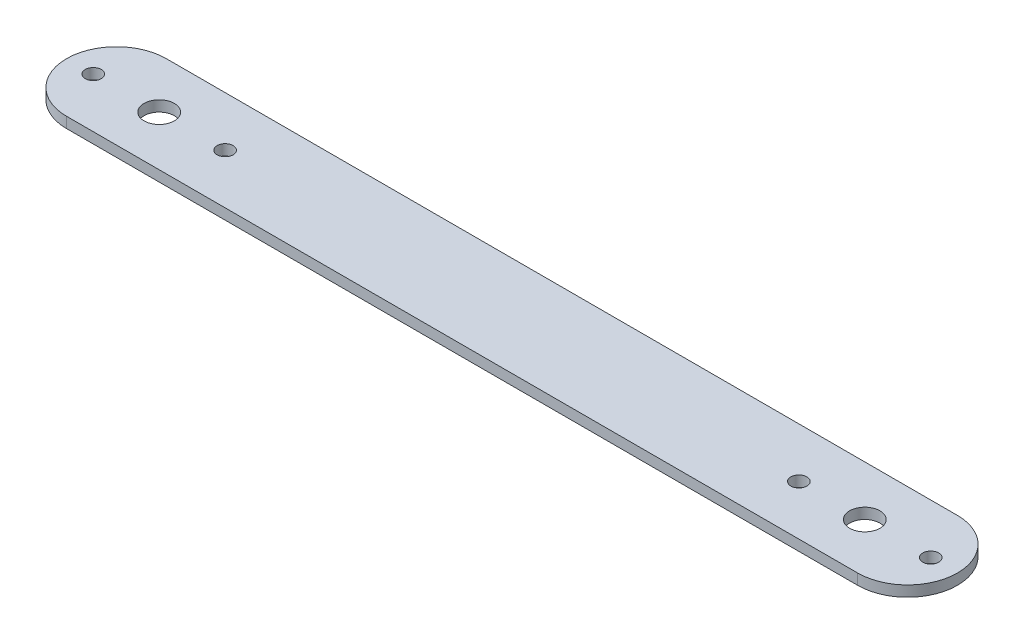
SolidWorks part; units mm, degrees
ref_plane "前视" through (0, 0, 0) normal (0, 0, 1) x (1, 0, 0)
ref_plane "上视" through (0, 0, 0) normal (0, 1, 0) x (1, 0, 0)
ref_plane "右视" through (0, 0, 0) normal (1, 0, 0) x (0, 0, -1)
sketch "草图1" plane through (0, 0, 0) normal (0, 1, 0) x (1, 0, 0)
  line L1 (-125, 14) -> (125, 14)
  line L2 (-125, 14) -> (-125, -14)
  line L3 (-125, -14) -> (125, -14)
  line L4 (125, 14) -> (125, -14)
  line L5 (-125, 14) -> (125, -14) construction
  line L6 (-125, -14) -> (125, 14) construction
  point P0 (0, 0)
  dimension "D1" = 250
  dimension "D2" = 28
extrude "凸台-拉伸1" add sketch "草图1" along normal blind 3 contours L2 | L2 | L3 L1 | L4 | L4 region at (0, 0, 0)
sketch "草图2" plane through (0, 3, 0) normal (0, 1, 0) x (1, 0, 0)
  circle A0 centre (-99, 0) radius 4.25
  circle A1 centre (99, 0) radius 4.25
  circle A2 centre (-33, 0) radius 4.25 construction
  circle A3 centre (33, 0) radius 4.25 construction
  dimension "D1" = 8.5
  dimension "D2" = 8.5
  dimension "D5" = 8.5
  dimension "D4" = 8.5
  dimension "D3" = 198
  dimension "D6" = 66
  dimension "D7" = 33
  dimension "D8" = 33
extrude "切除-拉伸1" cut sketch "草图2" against normal up to next
sketch "草图3" plane through (0, 3, 0) normal (0, 1, 0) x (1, 0, 0)
  circle A0 centre (-117.5, 0) radius 2.25
  circle A1 centre (-80.5, 0) radius 2.25
  circle A2 centre (80.5, 0) radius 2.25
  circle A3 centre (117.5, 0) radius 2.25
  circle A4 centre (-99, 0) radius 4.25 construction
  circle A5 centre (99, 0) radius 4.25 construction
  dimension "D2" = 18.5
  dimension "D3" = 4.5
  dimension "D4" = 4.5
  dimension "D6" = 18.5
  dimension "D7" = 4.5
  dimension "D8" = 4.5
  dimension "D1" = 37
  dimension "D5" = 37
extrude "切除-拉伸2" cut sketch "草图3" against normal up to next
sketch "草图4" plane through (0, 0, 0) normal (0, -1, 0) x (-1, 0, 0)
  circle A0 centre (66, 0) radius 4.25
  circle A1 centre (0, 0) radius 4.25
  circle A2 centre (-66, 0) radius 4.25
  dimension "D1" = 8.5
  dimension "D2" = 8.5
  dimension "D3" = 8.5
  dimension "D4" = 66
  dimension "D5" = 66
extrude "切除-拉伸3" [suppressed] cut sketch "草图4" against normal up to next
fillet "圆角1" 2 edges at (-125, 1.5, 14) (-125, 1.5, -14) type full round first side face at (0, 1.5, 14) second side face at (0, 1.5, -14) middle face at (-125, 1.5, 0)
fillet "圆角2" 2 edges at (125, 1.5, 14) (125, 1.5, -14) type full round first side face at (7, 1.5, 14) second side face at (7, 1.5, -14) middle face at (125, 1.5, 0)
